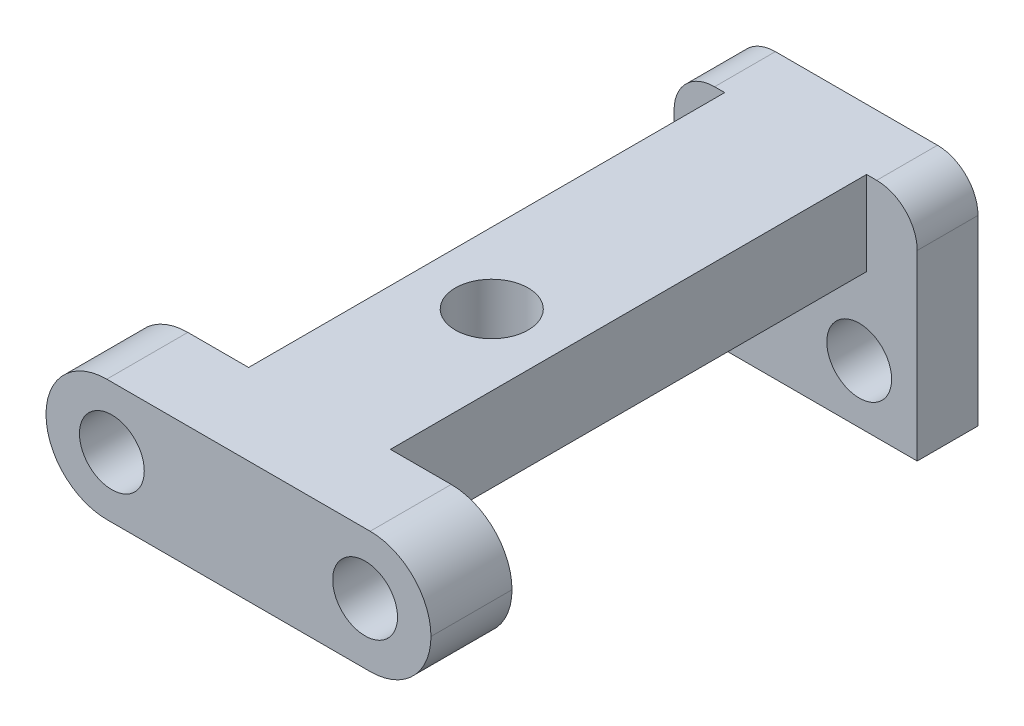
SolidWorks part; units mm, degrees
ref_plane "Front Plane" through (0, 0, 0) normal (0, 0, 1) x (1, 0, 0)
ref_plane "Top Plane" through (0, 0, 0) normal (0, 1, 0) x (1, 0, 0)
ref_plane "Right Plane" through (0, 0, 0) normal (1, 0, 0) x (0, 0, -1)
sketch "Sketch1" plane through (0, 0, 0) normal (0, 0, 1) x (1, 0, 0)
  line L0 (-3.5, 39.8466) -> (-3.5, 44)
  line L1 (-3.5, 44) -> (3.5, 44)
  line L2 (3.5, 44) -> (3.5, 39.8466)
  circle A0 centre (0, 0) radius 40
  dimension "D1" = 80
  dimension "D2" = 44
  dimension "D3" = 7
  dimension "D4" = 3.5
extrude "Boss-Extrude1" add sketch "Sketch1" along normal blind 27.5 contours A0 L2 L1 L0 region at (0, 41.9742, 0)
sketch "Sketch2" plane through (0, 0, 0) normal (0, 0, -1) x (-1, 0, 0)
  line L0 (0, 0) -> (0, 36) construction
  line L1 (-6, 44) -> (6, 44)
  line L2 (-6, 44) -> (-6, 33)
  line L3 (-6, 33) -> (6, 33)
  line L4 (6, 44) -> (6, 33)
  line L5 (-3.5, 44) -> (-3.5, 39.8466) construction
  line L6 (0, 0) -> (3.1376, 35.863) construction
  line L7 (3.5, 44) -> (-3.5, 44) construction
  line L8 (0, 0) -> (-3.1376, 35.863) construction
  circle A0 centre (-3.1376, 35.863) radius 1.6
  circle A1 centre (3.1376, 35.863) radius 1.6
  circle A2 centre (0, 0) radius 36
  arc M5 (-3.5, 39.8466) -> (3.5, 39.8466) centre (0, 0) cw
  line M6 (3.5, 39.8466) -> (3.5, 44)
  line M7 (3.5, 44) -> (-3.5, 44)
  line M8 (-3.5, 44) -> (-3.5, 39.8466)
  dimension "D2" = 72
  dimension "D3" = 5
  dimension "D1" = 11
  dimension "D4" = 5
  dimension "D8" = 12
  dimension "D9" = 2.5
extrude "Boss-Extrude2" add sketch "Sketch2" along normal blind 3 contours L4 A2 A1 A0 L2 L3 | A2 L4 L1 L2 A0 A1 M6 M5 M8 | M8 M5 M6 M7 region at (0, 39.4121, 0) region at (0, 41.9742, 0) region at (0, 34.1877, 0)
sketch "Sketch3" plane through (0, 0, 27.5) normal (0, 0, 1) x (1, 0, 0)
  line L0 (0, 44) -> (0, 34.329) construction
  line L1 (-3.5, 44) -> (3.5, 44) construction
  line L3 (-9.5, 44) -> (9.5, 44)
  line L4 (-9.5, 44) -> (-9.5, 38)
  line L5 (-9.5, 38) -> (9.5, 38)
  line L6 (9.5, 44) -> (9.5, 38)
  dimension "D1" = 6
  dimension "D2" = 19
extrude "Boss-Extrude3" add sketch "Sketch3" against normal blind 4
hole_wizard "M3 Clearance Hole1" positions "Sketch4" profile "Sketch5" hole size "M3" standard "ANSI Metric" end condition up to next
sketch "Sketch4" plane through (0, 0, 27.5) normal (0, 0, 1) x (1, 0, 0)
  line L0 (-9.5, 44) -> (-9.5, 38) construction
  line L1 (9.5, 38) -> (9.5, 44) construction
  line L2 (-9.5, 44) -> (9.5, 44) construction
  point P0 (-6.25, 41)
  point P2 (6.25, 41)
  dimension "D1" = 3.25
  dimension "D2" = 3.25
  dimension "D3" = 3
  dimension "D4" = 3
sketch "Sketch5" plane through (-6.25, 41, 27.5) normal (1, 0, 0) x (0, -1, 0)
  line L0 (0, 0) -> (0, 4)
  line L1 (0, 4) -> (1.6, 4)
  line L2 (1.6, 4) -> (1.6, 0)
  line L5 (1.6, 0) -> (0, 0)
  line L11 (0, -6.35) -> (0, 107.95) construction
  dimension "Thru Hole Dia." = 3.2
  dimension "Thru Hole Depth" = 4
fillet "Fillet1" radius 3 4 edges at (9.5, 38, 25.5) (9.5, 44, 25.5) (-9.5, 38, 25.5) (-9.5, 44, 25.5)
hole_wizard "M3 Clearance Hole2" positions "Sketch6" profile "Sketch7" hole size "M3" standard "ANSI Metric" end condition through all
sketch "Sketch6" plane through (0, 44, 0) normal (0, 1, 0) x (1, 0, 0)
  line L2 (0, -15) -> (3.5, -15) construction
  line L3 (3.5, -23.5) -> (3.5, 0) construction
  line L4 (0, -15) -> (-3.5, -15) construction
  line L5 (-3.5, -23.5) -> (-3.5, 0) construction
  line L6 (6, 3) -> (-6, 3) construction
  line L7 (0, 0) -> (0, -22.8602) construction
  point P0 (0, -15)
  point P28 (0, -15)
  dimension "D1" = 18
sketch "Sketch7" plane through (0, 44, 15) normal (1, 0, 0) x (0, 0, 1)
  line L0 (0, 0) -> (0, 11)
  line L1 (0, 11) -> (1.8, 11)
  line L2 (1.8, 11) -> (1.8, 0)
  line L5 (1.8, 0) -> (0, 0)
  line L11 (0, -6.35) -> (0, 107.95) construction
  dimension "Thru Hole Dia." = 3.6
  dimension "Thru Hole Depth" = 11
fillet "Fillet2" radius 2 2 edges at (6, 44, -1.5) (-6, 44, -1.5)
